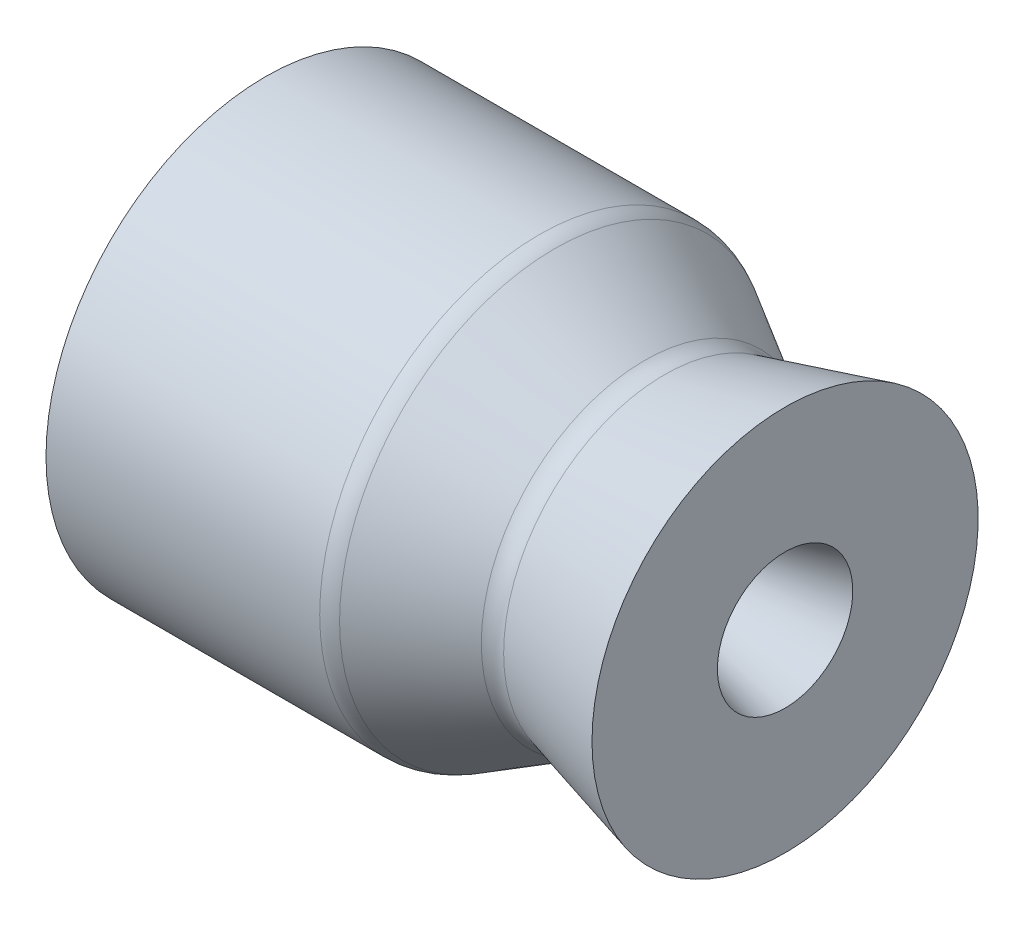
SolidWorks part; units mm, degrees
material "AISI 304"
ref_plane "Front Plane" through (0, 0, 0) normal (0, 0, 1) x (1, 0, 0)
ref_plane "Top Plane" through (0, 0, 0) normal (0, 1, 0) x (1, 0, 0)
ref_plane "Right Plane" through (0, 0, 0) normal (1, 0, 0) x (0, 0, -1)
sketch "chamberNozzle" plane through (0, 0, 0) normal (0, 0, 1) x (1, 0, 0)
  line L0 (0, 0) -> (366.3783, 0) construction
  line L1 (0, 0) -> (0, 38.1) construction
  line L2 (0, 38.1) -> (110.897, 38.1)
  line L3 (158.9188, 24.511) -> (158.9188, 13.97) construction
  line L4 (117.247, 36.3985) -> (153.6483, 15.3822)
  line L5 (150.9294, 13.97) -> (106.9103, 13.97) construction
  line L6 (161.647, 14.3292) -> (210.5452, 27.4314)
  line L7 (210.5452, 27.4314) -> (210.5452, 0) construction
  line L8 (0, 88.9) -> (110.897, 88.9)
  line L9 (117.247, 87.1985) -> (153.6483, 66.1822)
  line L10 (161.647, 65.1292) -> (210.5452, 78.2314)
  line L11 (0, 38.1) -> (0, 45.72)
  line L12 (0, 45.72) -> (5.08, 45.72)
  line L13 (5.08, 45.72) -> (5.08, 55.88)
  line L14 (5.08, 55.88) -> (0, 55.88)
  line L15 (0, 55.88) -> (0, 88.9)
  line L17 (210.5452, 78.2314) -> (210.5452, 27.4314)
  arc A0 (153.6483, 15.3822) -> (161.647, 14.3292) centre (158.9188, 24.511) ccw
  arc A1 (110.897, 38.1) -> (117.247, 36.3985) centre (110.897, 25.4) cw
  arc A2 (153.6483, 66.1822) -> (161.647, 65.1292) centre (158.9188, 75.311) ccw
  arc A3 (110.897, 88.9) -> (117.247, 87.1985) centre (110.897, 76.2) cw
  point P16 (114.3, 38.1)
  point P28 (5.08, 50.8)
  dimension "D4" = 21.082
  dimension "D9" = 12.7
  dimension "D1" = 38.1
  dimension "D3" = 13.97
  dimension "D5" = 30
  dimension "D6" = 15
  dimension "D10" = 50.8
  dimension "D11" = 10.16
  dimension "D12" = 5.08
  dimension "D13" = 12.7
revolve "Revolve1" add sketch "chamberNozzle" angle 360 about L0
ref_plane "chamberInterface" through (0, 0, 0) normal (-1, 0, 0) x (0, 0, 1)
sketch "Sketch1" plane through (0, 0, 0) normal (-1, 0, 0) x (0, 0, 1)
  circle A0 centre (0, 0) radius 72.39 construction
  dimension "D1" = 144.78
hole_wizard "1/2 (0.5) Diameter Hole1" positions "Sketch2" profile "Sketch3" hole size "1/2" standard "ANSI Inch"
sketch "Sketch2" plane through (0, 0, 0) normal (-1, 0, 0) x (0, 0, 1)
  circle A0 centre (0, 0) radius 72.39 construction
  point P0 (-72.39, 0)
sketch "Sketch3" plane through (0, 0, -72.39) normal (0, 1, 0) x (0, 0, 1)
  line L0 (0, 0) -> (0, 16.5155)
  line L1 (0, 16.5155) -> (6.35, 12.7)
  line L2 (6.35, 12.7) -> (6.35, 0.635)
  line L3 (6.35, 0.635) -> (6.985, 0)
  line L5 (6.985, 0) -> (0, 0)
  line L6 (-6.35, 0.635) -> (-6.985, 0) construction
  line L10 (0, 16.5155) -> (-6.35, 12.7) construction
  line L11 (0, -6.35) -> (0, 107.95) construction
  dimension "Hole Dia." = 12.7
  dimension "Hole Depth" = 12.7
  dimension "Near C'Sink Dia." = 13.97
  dimension "Near C'Sink Angle" = 90
  dimension "Drill Angle" = 118
pattern_circular "CirPattern1" count 6 over 360 about axis through (0, 0, 0) along (-1, 0, 0) of "1/2 (0.5) Diameter Hole1"
equation "\"l_star\"= .8m'characteristic length"
equation "\"R_t\"= .55in'throat radius"
equation "\"V_c\"= \"l_star\" * \"R_t\"'chamber volume"
equation "\"D_c\"= 3in'chamber diameter"
equation "\"L_c\"= \"V_c\" / ( ( pi * \"D_c\" ) / 4 )'chamber length"
equation "\"eps_x\"= 3.8557'expansion ratio"
equation "\"D_e\"= \"R_t\" * 2 * sqr ( \"eps_x\" )'exit diameter"
equation "\"arc_t\"= 1.5in * \"R_t\"'arc between convergent and divergent"
equation "\"D3@chamberNozzle\" = \"R_t\""
equation "\"D7@chamberNozzle\" = \"D_e\" / 2"
equation "\"D1@chamberNozzle\" = \"D_c\" / 2"
equation "\"D12@chamberNozzle\"=\"D11@chamberNozzle\"/2"
equation "\"D13@chamberNozzle\"=\"D10@chamberNozzle\"/4"
